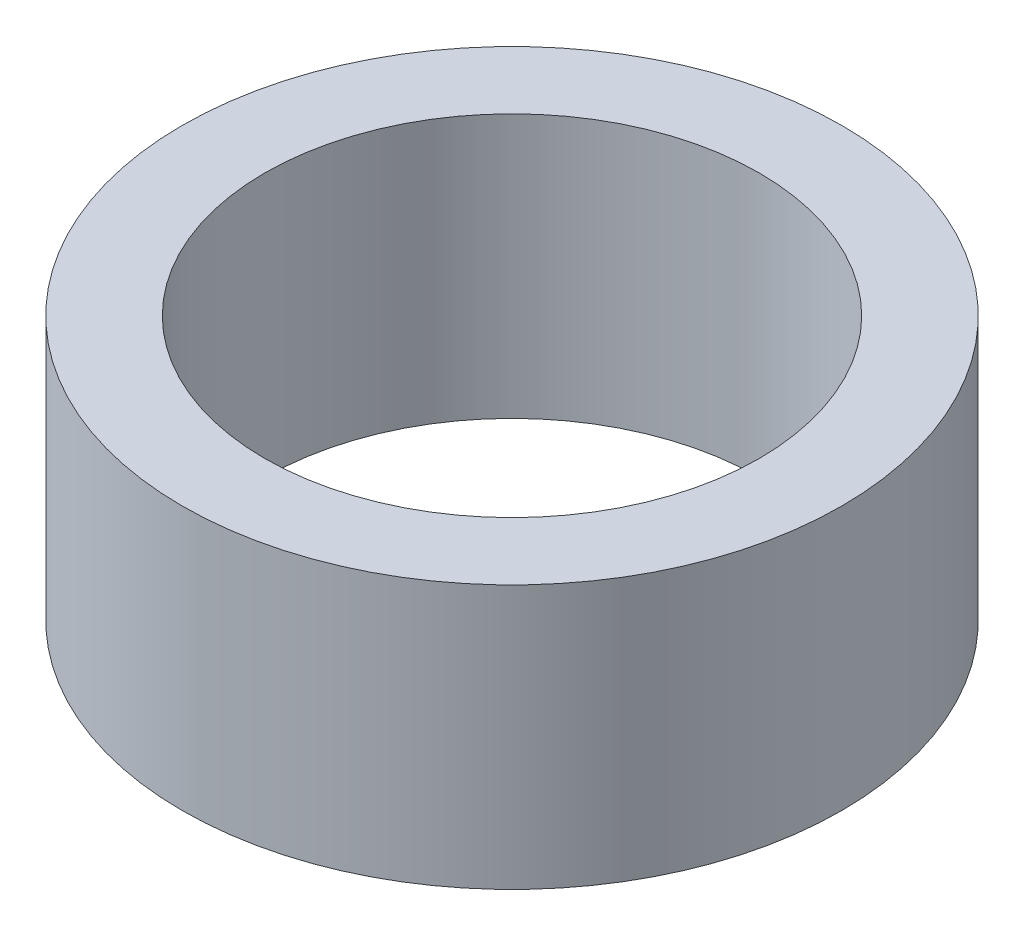
SolidWorks part; units mm, degrees
ref_plane "Front Plane" through (0, 0, 0) normal (0, 0, 1) x (1, 0, 0)
ref_plane "Top Plane" through (0, 0, 0) normal (0, 1, 0) x (1, 0, 0)
ref_plane "Right Plane" through (0, 0, 0) normal (1, 0, 0) x (0, 0, -1)
sketch "Sketch1" plane through (0, 0, 0) normal (0, 1, 0) x (1, 0, 0)
  circle A0 centre (0, 0) radius 30
  dimension "FLANGE_OD" = 60
extrude "Boss-Extrude1" add sketch "Sketch1" along normal blind 24
sketch "Sketch2" plane through (0, 0, 0) normal (0, 1, 0) x (1, 0, 0)
  circle A0 centre (0, 0) radius 22.5
  dimension "BORE_D" = 45
extrude "Cut-Extrude1" cut sketch "Sketch2" along normal through all
sketch "Sketch3" plane through (0, 24, 0) normal (0, 1, 0) x (1, 0, 0)
  circle A0 centre (0, 0) radius 12.9677 construction
  circle A1 centre (-12.9677, 0) radius 1.5
  dimension "BOLT_D" = 3
  dimension "BOLT_PCD" = 25.9355
extrude "Cut-Extrude2" cut sketch "Sketch3" against normal blind 23.727 rebuild error yes
pattern_circular "CirPattern1" count 5 over 360 rebuild error yes
